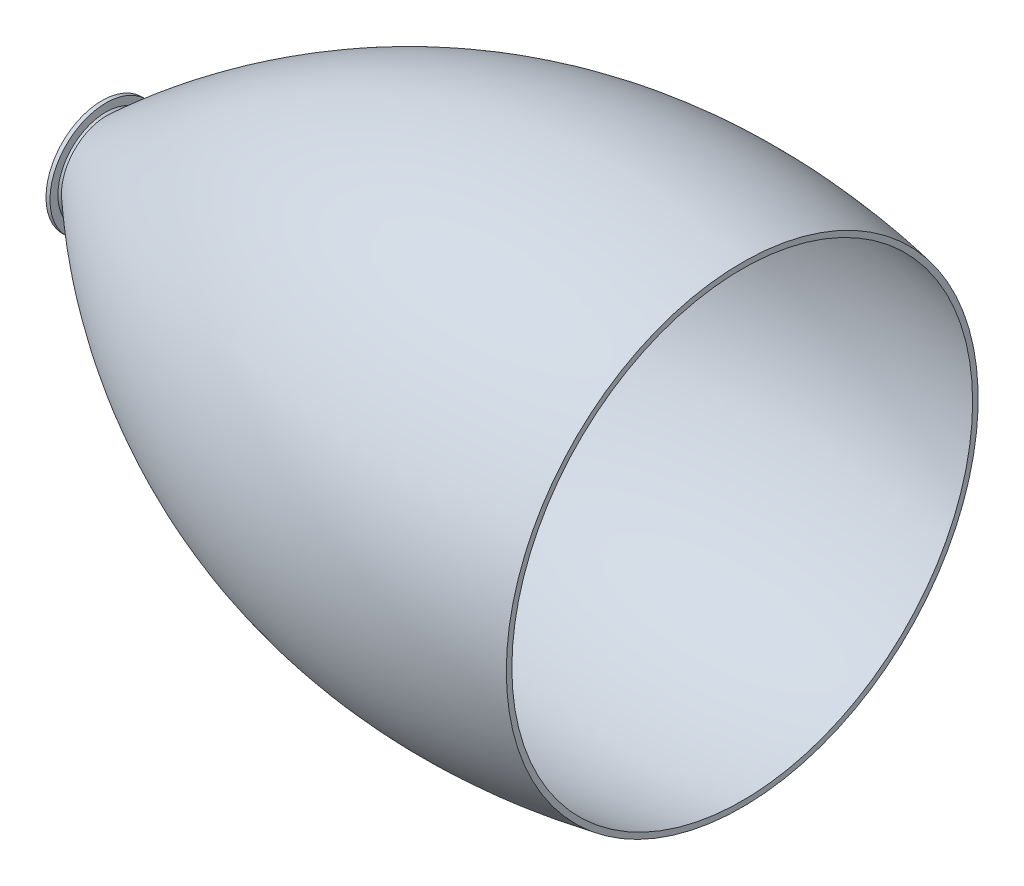
SolidWorks part; units mm, degrees
material "A286 Iron Base Superalloy"
ref_plane "Front Plane" through (0, 0, 0) normal (0, 0, 1) x (1, 0, 0)
ref_plane "Top Plane" through (0, 0, 0) normal (0, 1, 0) x (1, 0, 0)
ref_plane "Right Plane" through (0, 0, 0) normal (1, 0, 0) x (0, 0, -1)
sketch "Sketch1" plane through (0, 0, 0) normal (0, 0, 1) x (1, 0, 0)
  line L0 (-1229.8282, 0) -> (1426.3964, 0) construction
  line L1 (0, -63.5) -> (0, 63.5) construction
  line L2 (0, 0) -> (1016, 0) construction
  line L3 (1016, -368.3) -> (1016, 368.3) construction
  line L5 (1016, 377.19) -> (1016, 368.3)
  line L6 (0, -72.39) -> (0, -63.5)
  line L7 (1016, -377.19) -> (1016, -368.3)
  line L8 (-412.8242, -144.8099) -> (-412.8242, 144.8099) construction
  line L9 (-412.8242, 144.8099) -> (-412.8242, 153.6999)
  line L10 (-412.8242, -144.8099) -> (-412.8242, -153.6999)
  spline S0 degree 2 poles (0, 63.5) (448.5492, 461.9788) (1016, 368.3) knots 0 0 0 1 1 1
  spline S1 degree 2 poles (0, -63.5) (448.5492, -461.9788) (1016, -368.3) knots 0 0 0 1 1 1
  spline S2 degree 2 poles (0, -72.39) (446.4179, -483.3057) (1016, -377.19) knots 0 0 0 1 1 1
  spline S3 degree 2 poles (0, -63.5) (448.5492, -461.9788) (1016, -368.3) knots 0 0 0 1 1 1
  spline S4 degree 2 poles (0, 72.39) (446.4179, 483.3057) (1016, 377.19) knots 0 0 0 1 1 1
  spline S5 degree 2 poles (0, 63.5) (-192.2835, 162.6782) (-412.8242, 144.8099) knots 0 0 0 1 1 1
  spline S6 degree 2 poles (0, -63.5) (-192.2835, -162.6782) (-412.8242, -144.8099) knots 0 0 0 1 1 1
  spline S7 degree 2 poles (0, -72.39) (-189.3535, -181.7828) (-412.8242, -153.6999) knots 0 0 0 1 1 1
  spline S9 degree 2 poles (0, 72.39) (-189.3535, 181.7828) (-412.8242, 153.6999) knots 0 0 0 1 1 1
  point P8 (0, 0)
  point P14 (1016, 0)
  point P22 (-412.8242, 0)
  dimension "D4" = 8.89
  dimension "D1" = 127
  dimension "D2" = 1016
  dimension "D3" = 736.6
  dimension "D5" = 8.89
  dimension "D6" = 8.89
  dimension "D7" = 289.6197
revolve "Revolve3" add sketch "Sketch1" angle 360 about L0 region at (1001.3232, 372.745, 0)
ref_plane "Plane1" through (0, 0, 0) normal (1, 0, 0) x (0, 0, -1)
ref_plane "Plane2" through (-7.62, 0, 0) normal (-1, 0, 0) x (0, 0, 1)
sketch "Sketch4" plane through (-7.62, 0, 0) normal (-1, 0, 0) x (0, 0, 1)
  line L1 (-1213.2286, 638.9142) -> (1085.9115, 638.9142)
  line L2 (-1213.2286, 638.9142) -> (-1213.2286, -445.9528)
  line L3 (-1213.2286, -445.9528) -> (1085.9115, -445.9528)
  line L4 (1085.9115, 638.9142) -> (1085.9115, -445.9528)
extrude "Cut-Extrude1" cut sketch "Sketch4" along normal blind 554.228
sketch "Sketch5" plane through (-7.62, 0, 0) normal (-1, 0, 0) x (0, 0, 1)
  circle A0 centre (0, 0) radius 89.4288
  circle A1 centre (0, 0) radius 76.7288 construction
  circle A2 centre (0, 0) radius 76.7288
  dimension "D1" = 12.7
extrude "Boss-Extrude1" add sketch "Sketch5" against normal blind 6.35 separate body
